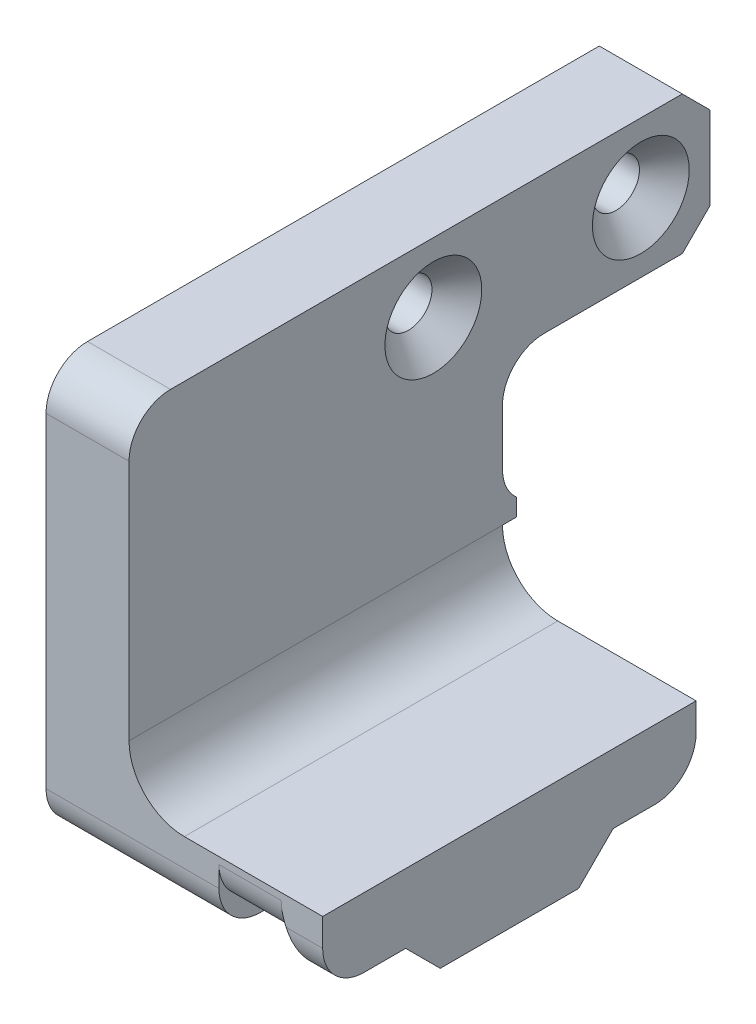
SolidWorks part; units mm, degrees
material "3D printed plastic"
ref_plane "Front Plane" through (0, 0, 0) normal (0, 0, 1) x (1, 0, 0)
ref_plane "Top Plane" through (0, 0, 0) normal (0, 1, 0) x (1, 0, 0)
ref_plane "Right Plane" through (0, 0, 0) normal (1, 0, 0) x (0, 0, -1)
sketch "Sketch1" plane through (0, 0, 0) normal (0, 0, 1) x (1, 0, 0)
  line L0 (0, 0) -> (0, 20.5)
  line L1 (0, 20.5) -> (-6, 20.5)
  line L2 (-6, 20.5) -> (-6, -9)
  line L3 (-6, -9) -> (14, -9)
  line L4 (14, -9) -> (14, -4)
  line L5 (14, -4) -> (4, -4)
  arc A0 (4, -4) -> (0, 0) centre (4, 0) cw
  dimension "D3" = 4
  dimension "D1" = 6
  dimension "D2" = 5
  dimension "D4" = 20
  dimension "D5" = 24.5
extrude "Boss-Extrude1" add sketch "Sketch1" along normal mid plane 42
sketch "Sketch2" plane through (0, 0, 0) normal (1, 0, 0) x (0, 0, -1)
  line L0 (1, 15.5) -> (16, 15.5) construction
  line L1 (16, 15.5) -> (21, 15.5) construction
  line L2 (21, 0) -> (21, 20.5) construction
  line L3 (-21, 20.5) -> (21, 20.5) construction
  circle A0 centre (16, 15.5) radius 1.7
  circle A1 centre (1, 15.5) radius 1.7
  dimension "D1" = 3.4
  dimension "D2" = 5
  dimension "D3" = 15
  dimension "D4" = 5
extrude "Cut-Extrude1" cut sketch "Sketch2" against normal through all
sketch "Sketch3" plane through (14, 0, 0) normal (1, 0, 0) x (0, 0, -1)
  line L0 (-21, -9) -> (21, -9) construction
  line L1 (6, -9) -> (21, -9)
  line L2 (6, -9) -> (6, 10.5)
  line L3 (6, 10.5) -> (21, 10.5)
  line L4 (21, -9) -> (21, 10.5)
  line L5 (21, 0) -> (21, 20.5) construction
  line L6 (-21, 20.5) -> (21, 20.5) construction
  line L7 (-21, -9) -> (-21, -4) construction
  dimension "D1" = 10
  dimension "D2" = 27
extrude "Cut-Extrude2" cut sketch "Sketch3" against normal through all
sketch "Sketch4" plane through (0, 0, 0) normal (1, 0, 0) x (0, 0, -1)
  circle A0 centre (1, 15.5) radius 3.5
  circle A1 centre (16, 15.5) radius 3.5
  dimension "D1" = 7
extrude "Cut-Extrude3" cut sketch "Sketch4" against normal blind 40 draft 45
sketch "Sketch5" plane through (14, 0, 0) normal (1, 0, 0) x (0, 0, -1)
  line L0 (-21, -9) -> (-21, -4.5)
  line L1 (-21, -9) -> (-21, -4) construction
  line L2 (-18, -7.5) -> (3, -7.5)
  line L3 (6, -4) -> (6, -9) construction
  line L4 (6, -4.5) -> (6, -9)
  line L5 (6, -9) -> (-21, -9)
  arc A0 (-21, -4.5) -> (-18, -7.5) centre (-18, -4.5) ccw
  arc A1 (3, -7.5) -> (6, -4.5) centre (3, -4.5) ccw
  dimension "D2" = 3
  dimension "D1" = 1.5
extrude "Cut-Extrude4" cut sketch "Sketch5" against normal blind 6 from offset 1.5 offset against normal yes
fillet "Fillet1" radius 3 4 edges at (0.25, -9, 21) (13.25, -9, 21) (0.25, -9, -6) (13.25, -9, -6)
sketch "Sketch6" plane through (14, 0, 0) normal (1, 0, 0) x (0, 0, -1)
  line L0 (-15, -9) -> (0, -9)
  line L1 (-18, -9) -> (3, -9) construction
  line L2 (0, -9) -> (-2.5, -11.5)
  line L3 (-2.5, -11.5) -> (-12.5, -11.5)
  line L4 (-12.5, -11.5) -> (-15, -9)
  line L5 (-7.5, -9) -> (-7.5, -11.5) construction
  line L6 (-18, -9) -> (3, -9) construction
  dimension "D1" = 2.5
  dimension "D2" = 15
extrude "Boss-Extrude2" add sketch "Sketch6" against normal up to surface (20 mm away) up to face at (-6, 15.5, -2.7)
fillet "Fillet2" radius 1 2 edges at (9.5, -9, 0) (9.5, -9, 15)
chamfer "Chamfer1" distance 1.5 angle 45 3 edges at (12.5, -6.6213, -5.1213) (12.5, -6.6213, 20.1213) (12.5, -7.5, 7.5)
fillet "Fillet3" radius 3 2 edges at (-3, 10.5, -6) (-3, 20.5, 21)
chamfer "Chamfer2" distance 2 angle 45 2 edges at (-3, 10.5, -21) (-3, 20.5, -21)
sketch "Sketch7" plane through (0, 0, 0) normal (1, 0, 0) x (0, 0, -1)
  line L0 (6, 3.5) -> (6, 0)
  line L1 (6, 0) -> (6, 7.5) construction
  line L2 (6, 0) -> (7, 0)
  line L3 (7, 0) -> (7, 1.2639)
  line L4 (-21, 0) -> (6, 0) construction
  arc A0 (6, 3.5) -> (7, 1.2639) centre (9, 3.5) ccw
  arc A1 (9, 10.5) -> (6, 7.5) centre (9, 7.5) ccw construction
  dimension "D1" = 1
  dimension "D2" = 4
extrude "Boss-Extrude3" add sketch "Sketch7" against normal up to surface (6 mm away) up to face at (-6, 15.5, -2.7)
